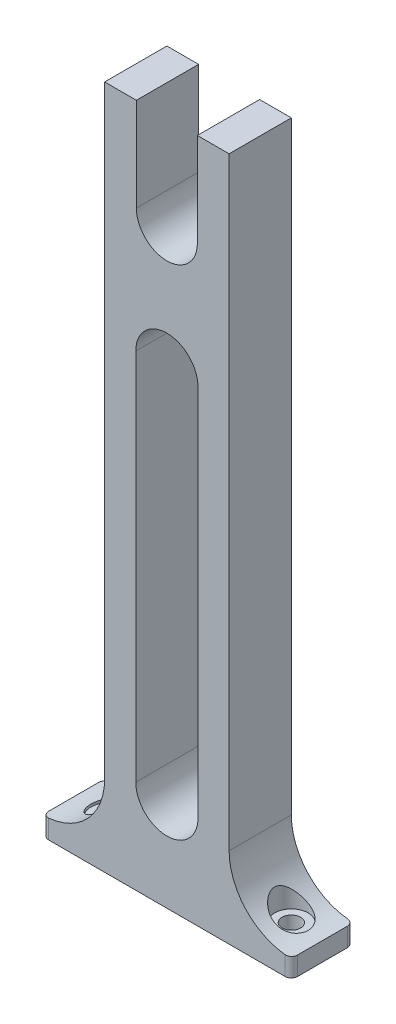
SolidWorks part; units mm, degrees
ref_plane "Front Plane" through (0, 0, 0) normal (0, 0, 1) x (1, 0, 0)
ref_plane "Top Plane" through (0, 0, 0) normal (0, 1, 0) x (1, 0, 0)
ref_plane "Right Plane" through (0, 0, 0) normal (1, 0, 0) x (0, 0, -1)
sketch "Sketch2" plane through (0, 0, 0) normal (0, 1, 0) x (1, 0, 0)
  line L1 (10, -5) -> (-10, -5)
  line L2 (10, -5) -> (10, 5)
  line L3 (10, 5) -> (-10, 5)
  line L4 (-10, -5) -> (-10, 5)
  line L5 (10, -5) -> (-10, 5) construction
  line L6 (10, 5) -> (-10, -5) construction
  point P0 (0, 0)
  dimension "D1" = 10
  dimension "D2" = 20
extrude "Boss-Extrude1" add sketch "Sketch2" along normal blind 110
sketch "Sketch3" plane through (0, 0, 5) normal (0, 0, 1) x (1, 0, 0)
  line L0 (-4.9, 110) -> (-4.9, 95)
  line L1 (-10, 110) -> (10, 110) construction
  line L2 (4.9, 95) -> (4.9, 110)
  line L3 (4.9, 110) -> (-4.9, 110)
  line L4 (-10, 0) -> (10, 0) construction
  arc A0 (-4.9, 95) -> (4.9, 95) centre (0, 95) ccw
  dimension "D2" = 4.9
  dimension "D1" = 95
extrude "Cut-Extrude1" cut sketch "Sketch3" against normal up to surface (10 mm away) up to face at (0, 55, -5)
sketch "Sketch5" plane through (0, 0, 5) normal (0, 0, 1) x (1, 0, 0)
  line L0 (0, 0) -> (0, 90.1) construction
  line L1 (-5, 15.05) -> (5, 15.05)
  line L2 (-5, 15.05) -> (-5, 75.05)
  line L3 (-5, 75.05) -> (5, 75.05)
  line L4 (5, 15.05) -> (5, 75.05)
  line L5 (-5, 15.05) -> (5, 75.05) construction
  line L6 (-5, 75.05) -> (5, 15.05) construction
  arc A0 (-5, 75.05) -> (5, 75.05) centre (0, 75.05) cw
  arc A1 (-5, 15.05) -> (5, 15.05) centre (0, 15.05) ccw
  arc A2 (-4.9, 95) -> (4.9, 95) centre (0, 95) ccw construction
  point P0 (0, 45.05)
  point P14 (0, 45.05)
  dimension "D1" = 5
  dimension "D2" = 60
extrude "Cut-Extrude2" cut sketch "Sketch5" against normal up to surface (10 mm away) contours L1 A1 | L1 L4 L3 L2 | A0 L3 region at (0, 45.05, 5) region at (0, 12.9279, 5) region at (0, 77.1721, 5) up to face at (0, 78.1375, -5)
sketch "Sketch6" plane through (10, 0, 0) normal (1, 0, 0) x (0, 0, -1)
  line L0 (5, 110) -> (5, 0) construction
  line L1 (-5, 0) -> (5, 0)
  line L2 (-5, 0) -> (-5, 3)
  line L3 (-5, 3) -> (5, 3)
  line L4 (5, 0) -> (5, 3)
  dimension "D1" = 3
extrude "Boss-Extrude2" add sketch "Sketch6" along normal blind 10
ref_plane "Plane1" through (0, 3, 0) normal (0, 1, 0) x (1, 0, 0)
fillet "Fillet2" radius 10 1 edges at (10, 3, 0)
sketch "Sketch19" plane through (0, 3, 0) normal (0, 1, 0) x (1, 0, 0)
  line L0 (15, 5) -> (15, -5) construction
  line L1 (10, -5) -> (20, -5) construction
  line L2 (20, 5) -> (10, 5) construction
  circle A0 centre (15, 0) radius 1.5
  circle A1 centre (15, 0) radius 2.7
  dimension "D1" = 3
  dimension "D2" = 5.4
extrude "Cut-Extrude5" cut sketch "Sketch19" against normal through all both and the other way through all contours A0
extrude "Cut-Extrude7" cut sketch "Sketch19<5>" along normal through all
sketch "Sketch19<5>" plane through (0, 3, 0) normal (0, 1, 0) x (1, 0, 0) same geometry as "Sketch19"
mirror "Mirror16" about plane through (0, 0, 0) normal (1, 0, 0) of "Boss-Extrude2"
fillet "Fillet1" radius 1 4 edges at (20, 1.5, -5) (20, 1.5, 5) (-20, 1.5, -5) (-20, 1.5, 5)
fillet "Fillet3" radius 10 1 edges at (-10, 3, 0)
sketch "Sketch20" plane through (0, 3, 0) normal (0, 1, 0) x (1, 0, 0)
  line L0 (-14.5, 5) -> (-14.5, -5) construction
  line L1 (-10, 5) -> (-19, 5) construction
  line L2 (-19, -5) -> (-10, -5) construction
  circle A0 centre (-14.5, 0) radius 1.5
  circle A1 centre (-14.5, 0) radius 2.7
  dimension "D1" = 3
  dimension "D2" = 5.4
extrude "Cut-Extrude8" cut sketch "Sketch20" against normal through all both and the other way through all contours A0
extrude "Cut-Extrude9" cut sketch "Sketch20<3>" along normal through all
sketch "Sketch20<3>" plane through (0, 3, 0) normal (0, 1, 0) x (1, 0, 0) same geometry as "Sketch20"
